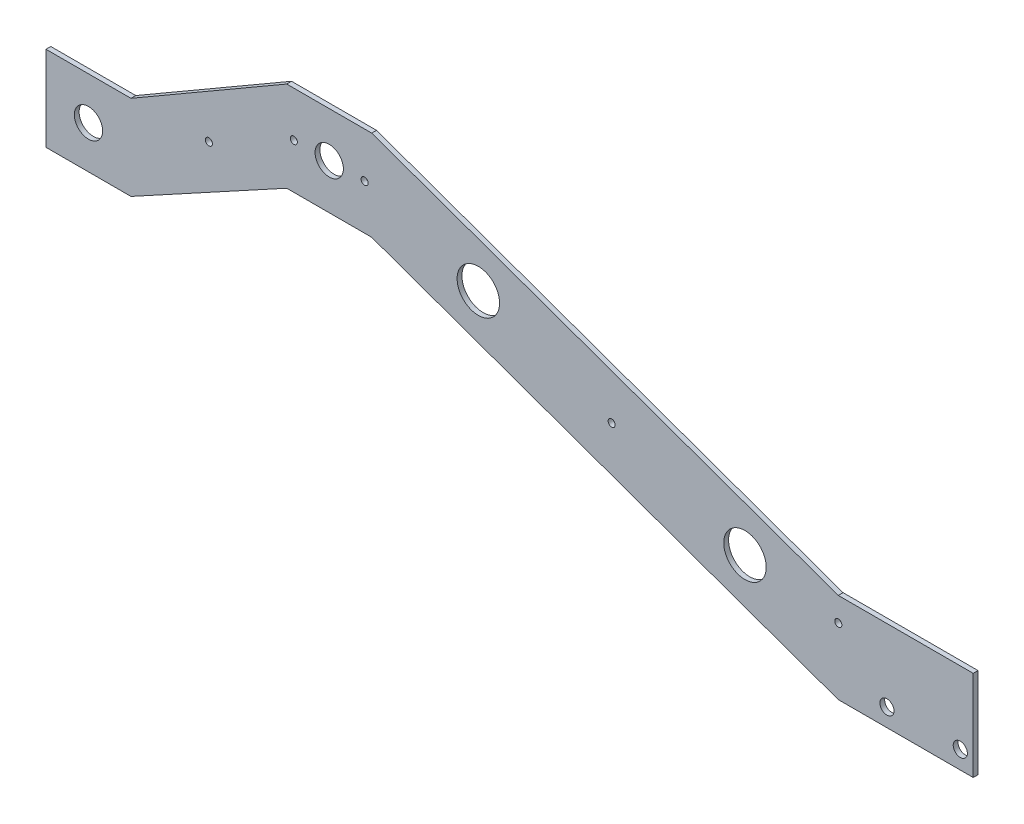
SolidWorks part; units mm, degrees
material "1060 Alloy"
ref_plane "Front Plane" through (0, 0, 0) normal (0, 0, 1) x (1, 0, 0)
ref_plane "Top Plane" through (0, 0, 0) normal (0, 1, 0) x (1, 0, 0)
ref_plane "Right Plane" through (0, 0, 0) normal (1, 0, 0) x (0, 0, -1)
sketch "Sketch1" plane through (0, 0, 0) normal (0, 0, 1) x (1, 0, 0)
  line L0 (0, 63.7314) -> (0, 0)
  line L1 (0, 63.7314) -> (-95.2463, 63.7314)
  line L2 (0, 0) -> (-95.2463, 0)
  line L3 (-95.2463, 63.7314) -> (-424.7463, 181.7314)
  line L4 (-424.7463, 181.7314) -> (-484.7463, 181.7314)
  line L5 (-484.7463, 181.7314) -> (-484.7463, 118) construction
  line L6 (-484.7463, 118) -> (-424.7463, 118)
  line L7 (-424.7463, 118) -> (-95.2463, 0)
  line L8 (-424.7463, 181.7314) -> (-424.7463, 118) construction
  line L9 (-95.2463, 63.7314) -> (-95.2463, 0) construction
  line L10 (-484.7463, 181.7314) -> (-594.7463, 118)
  line L11 (-594.7463, 118) -> (-654.7463, 118)
  line L12 (-654.7463, 118) -> (-654.7463, 58)
  line L13 (-654.7463, 58) -> (-594.7463, 58)
  line L14 (-594.7463, 58) -> (-484.7463, 118)
  line L15 (-424.7463, 149.8657) -> (-95.2463, 31.8657) construction
  line L16 (-424.7463, 149.8657) -> (-484.7463, 149.8657) construction
  line L17 (-594.7463, 118) -> (-594.7463, 58) construction
  line L18 (-594.7463, 88) -> (-484.7463, 149.8657) construction
  line L19 (-594.7463, 88) -> (-654.7463, 88) construction
  line L20 (-349.438, 122.8964) -> (-349.438, 91.0307) construction
  line L21 (-255.2929, 89.1813) -> (-255.2929, 57.3156) construction
  line L22 (-161.1479, 55.4663) -> (-161.1479, 23.6006) construction
  line L23 (-539.7463, 118.9329) -> (-539.7463, 88) construction
  line L24 (-35, 0) -> (-35, 63.7314) construction
  line L25 (-35, 12.7) -> (-60.9, 12.7) construction
  circle A0 centre (-624.7463, 88) radius 10
  circle A1 centre (-454.7463, 149.8657) radius 10
  circle A2 centre (-539.7463, 118.9329) radius 2.5
  circle A3 centre (-161.1479, 55.4663) radius 15
  circle A4 centre (-255.2929, 89.1813) radius 2.5
  circle A5 centre (-349.438, 122.8964) radius 15
  circle A6 centre (-429.7463, 149.8657) radius 2.5
  circle A7 centre (-479.7463, 149.8657) radius 2.5
  circle A8 centre (-60.9, 12.7) radius 5
  circle A9 centre (-95.2463, 46.8657) radius 2.5
  circle A10 centre (-9.1, 12.7) radius 5
  dimension "D10" = 70
  dimension "D13" = 30
  dimension "D14" = 5
  dimension "D15" = 30
  dimension "D16" = 20
  dimension "D17" = 5
  dimension "D18" = 20
  dimension "D19" = 5
  dimension "D20" = 5
  dimension "D23" = 25.9
  dimension "D24" = 5
  dimension "D1" = 60
  dimension "D2" = 118
  dimension "D3" = 63.7314
  dimension "D4" = 329.5
  dimension "D5" = 60
  dimension "D6" = 60
  dimension "D7" = 60
  dimension "D8" = 110
  dimension "D9" = 58
  dimension "D11" = 100
  dimension "D12" = 100
  dimension "D21" = 25
  dimension "D22" = 25
  dimension "D25" = 12.7
  dimension "D26" = 35
  dimension "D27" = 15
base flange "Base-Flange1" sketch "Sketch1" thickness 3.4 reverse thickness direction no parameters "D1"=0.7366
sketch "Bend-Lines1" [suppressed] plane through (0, 0, 0) normal (0, 1, 0) x (1, 0, 0)
sketch "Bounding-Box1" [suppressed] plane through (0, 0, 0) normal (0, 1, 0) x (1, 0, 0)
sheet metal parameters "Sheet-Metal1" thickness 3.4 parameters "D1"=0.7366
flat pattern "Flat-Pattern1" [suppressed]
sketch "Bend-Lines2" plane through (0, 0, 0) normal (0, 1, 0) x (1, 0, 0)
sketch3d "Bounding-Box2" [suppressed]
  line L0 (-645.7645, 204.6431, 0) -> (14.1228, 136.2365, 0) construction
  line L1 (-660.9, 58.6379, 0) -> (-1.0127, -9.7686, 0) construction
  line L2 (-645.7645, 204.6431, 0) -> (-660.9, 58.6379, 0) construction
  line L3 (14.1228, 136.2365, 0) -> (-1.0127, -9.7686, 0) construction
